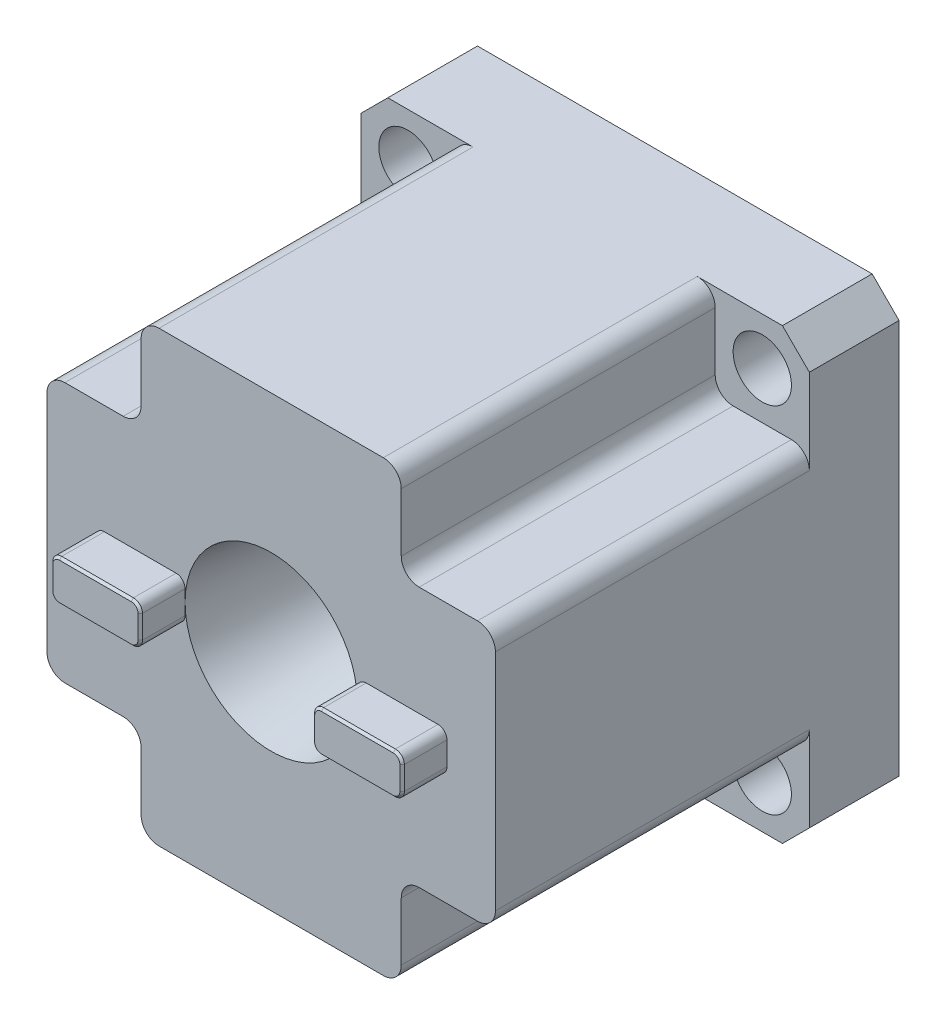
SolidWorks part; units mm, degrees
material "1.7147 (20MnCr5)"
ref_plane "前视基准面" through (0, 0, 0) normal (0, 0, 1) x (1, 0, 0)
ref_plane "上视基准面" through (0, 0, 0) normal (0, 1, 0) x (1, 0, 0)
ref_plane "右视基准面" through (0, 0, 0) normal (1, 0, 0) x (0, 0, -1)
other "Configuration Table"
sketch "草图1" plane through (0, 0, 0) normal (0, 0, 1) x (1, 0, 0)
  line L1 (0, 0) -> (50, 0)
  line L2 (0, 0) -> (0, -50)
  line L3 (0, -50) -> (50, -50)
  line L4 (50, 0) -> (50, -50)
  dimension "D1" = 50
  dimension "D2" = 50
extrude "凸台-拉伸1" add sketch "草图1" along normal blind 45
sketch "草图4" plane through (0, 0, 45) normal (0, 0, 1) x (1, 0, 0)
  line L0 (25, 0) -> (25, -50) construction
  line L1 (0, 0) -> (10.5, 0)
  line L2 (0, 0) -> (0, -10.5)
  line L3 (0, -10.5) -> (10.5, -10.5)
  line L4 (10.5, 0) -> (10.5, -10.5)
  line L5 (50, 0) -> (0, 0) construction
  line L6 (0, -50) -> (50, -50) construction
  line L7 (50, -25) -> (0, -25) construction
  line L8 (50, -50) -> (50, 0) construction
  line L9 (0, 0) -> (0, -50) construction
  line L10 (50, -10.5) -> (39.5, -10.5)
  line L11 (39.5, 0) -> (39.5, -10.5)
  line L12 (50, 0) -> (39.5, 0)
  line L13 (50, 0) -> (50, -10.5)
  line L14 (50, -50) -> (50, -39.5)
  line L15 (50, -50) -> (39.5, -50)
  line L16 (39.5, -50) -> (39.5, -39.5)
  line L17 (50, -39.5) -> (39.5, -39.5)
  line L18 (0, -39.5) -> (10.5, -39.5)
  line L19 (10.5, -50) -> (10.5, -39.5)
  line L20 (0, -50) -> (10.5, -50)
  line L21 (0, -50) -> (0, -39.5)
  dimension "D1" = 10.5
  dimension "D2" = 10.5
extrude "切除-拉伸1" cut sketch "草图4" against normal blind 35
fillet "圆角1" radius 2 12 edges at (0, -39.5, 27.5) (10.5, -39.5, 27.5) (10.5, -50, 27.5) (39.5, -50, 27.5) (39.5, -39.5, 27.5) (50, -39.5, 27.5) (50, -10.5, 27.5) (39.5, -10.5, 27.5) (39.5, 0, 27.5) (10.5, 0, 27.5) (10.5, -10.5, 27.5) (0, -10.5, 27.5)
chamfer "倒角1" distance 3 angle 45 4 edges at (50, -50, 5) (0, -50, 5) (0, 0, 5) (50, 0, 5)
sketch "草图5" plane through (0, 0, 10) normal (0, 0, 1) x (1, 0, 0)
  line L0 (0, -3) -> (0, -12.5) construction
  line L1 (12.5, 0) -> (3, 0) construction
  line L2 (25, 0) -> (25, -50) construction
  line L4 (37.5, 0) -> (12.5, 0) construction
  line L5 (12.5, -50) -> (37.5, -50) construction
  line L6 (0, -25) -> (50, -25) construction
  line L7 (0, -12.5) -> (0, -37.5) construction
  line L8 (50, -37.5) -> (50, -12.5) construction
  circle A0 centre (5.25, -5.25) radius 3.25
  circle A1 centre (44.75, -5.25) radius 3.25
  circle A2 centre (44.75, -44.75) radius 3.25
  circle A3 centre (5.25, -44.75) radius 3.25
  dimension "D3" = 6.5
  dimension "D1" = 5.25
  dimension "D2" = 5.25
extrude "切除-拉伸2" cut sketch "草图5" against normal through all
ref_plane "基准面1" through (25, 0, 0) normal (1, 0, 0) x (0, 0, -1)
sketch "草图6" plane through (25, 0, 0) normal (1, 0, 0) x (0, 0, -1)
  line L0 (0, -25) -> (-45, -25) construction
  line L1 (0, -47) -> (0, -3) construction
  line L2 (-45, -37.5) -> (-45, -12.5) construction
  line L3 (-45, -15.4) -> (-45, -25)
  line L4 (0, -25) -> (-45, -25)
  line L5 (-20.3143, -25) -> (-20.3143, -19) construction
  line L6 (-45, -15.4) -> (-20.3143, -19)
  line L7 (-20.3143, -19) -> (0, -19)
  line L10 (0, -19) -> (0, -25)
  dimension "D1" = 6
  dimension "D2" = 9.6
revolve "切除-旋转1" cut sketch "草图6" angle 360 about L0
sketch "草图7" plane through (0, 0, 45) normal (0, 0, 1) x (1, 0, 0)
  line L0 (0, -25) -> (50, -25) construction
  line L1 (0, -12.5) -> (0, -37.5) construction
  line L2 (50, -37.5) -> (50, -12.5) construction
  line L3 (34.6, -17.6463) -> (34.6, -32.8177) construction
  line L4 (25, -24.75) -> (25, 24.75) construction
  line L5 (34.6, -22.7) -> (44.6, -22.7)
  line L6 (34.6, -22.7) -> (34.6, -27.3)
  line L7 (34.6, -27.3) -> (44.6, -27.3)
  line L8 (44.6, -22.7) -> (44.6, -27.3)
  line L9 (15.4, -27.3) -> (5.4, -27.3)
  line L10 (5.4, -22.7) -> (5.4, -27.3)
  line L11 (15.4, -22.7) -> (5.4, -22.7)
  line L12 (15.4, -22.7) -> (15.4, -27.3)
  circle A0 centre (25, -25) radius 9.6 construction
  circle A1 centre (25, -25) radius 9.6 construction
  dimension "D1" = 10
  dimension "D2" = 4.6
  dimension "D3" = 2.3
extrude "凸台-拉伸4" add sketch "草图7" along normal blind 5
fillet "圆角2" radius 1 8 edges at (5.4, -22.7, 47.5) (5.4, -27.3, 47.5) (15.4, -27.3, 47.5) (15.4, -22.7, 47.5) (34.6, -22.7, 47.5) (44.6, -22.7, 47.5) (34.6, -27.3, 47.5) (44.6, -27.3, 47.5)
chamfer "倒角2" distance 0.25 angle 45 16 edges at (44.3071, -22.9929, 50) (44.6, -25, 50) (44.3071, -27.0071, 50) (39.6, -27.3, 50) (34.8929, -27.0071, 50) (34.6, -25, 50) (34.8929, -22.9929, 50) (39.6, -22.7, 50) (15.1071, -22.9929, 50) (15.4, -25, 50) (15.1071, -27.0071, 50) (10.4, -27.3, 50) (5.6929, -27.0071, 50) (5.4, -25, 50) (5.6929, -22.9929, 50) (10.4, -22.7, 50)
